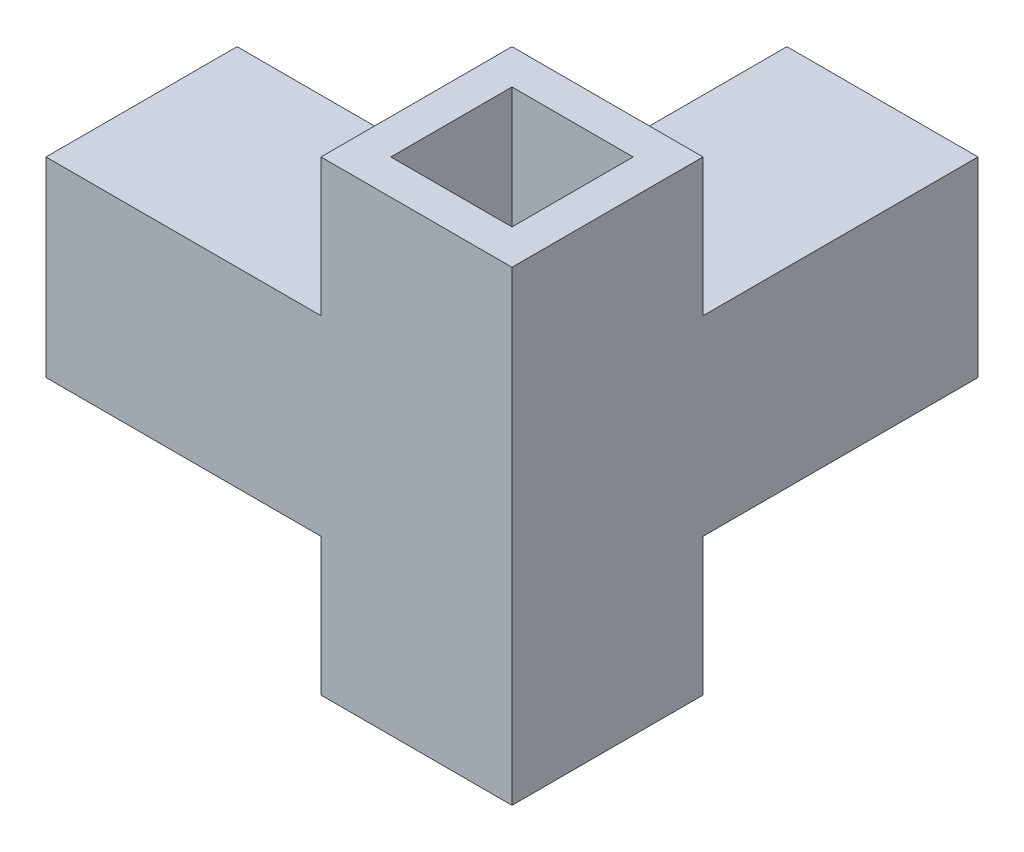
SolidWorks part; units mm, degrees
material "Ti-6Al-4VSolution treated and aged (SS)"
ref_plane "Front Plane" through (0, 0, 0) normal (0, 0, 1) x (1, 0, 0)
ref_plane "Top Plane" through (0, 0, 0) normal (0, 1, 0) x (1, 0, 0)
ref_plane "Right Plane" through (0, 0, 0) normal (1, 0, 0) x (0, 0, -1)
sketch "Sketch1" plane through (0, 0, 0) normal (1, 0, 0) x (0, 0, -1)
  line L0 (0, 0) -> (39.9501, 0) construction
  line L2 (0, 10) -> (0, -10)
  line L3 (0, -10) -> (8.2, -10)
  line L4 (8.2, 10) -> (8.2, 4.1)
  line L5 (0, 10) -> (8.2, 10)
  line L6 (8.2, -4.1) -> (20, -4.1)
  line L7 (8.2, 4.1) -> (20, 4.1)
  line L8 (0, 3.1861) -> (0, -3.1861)
  line L10 (20, 4.1) -> (20, -4.1)
  line L11 (8.2, -4.1) -> (8.2, -10)
  point P12 (0, -3.1861)
  point P14 (0, 0)
  dimension "D1" = 20
  dimension "D2" = 8.2
  dimension "D3" = 20
extrude "Boss-Extrude1" add sketch "Sketch1" along normal blind 8.2 contours L11 L3 L2 L5 L4 L7 L10 L6
shell "Shell1" thickness 1.5 removed face at (4.1, -10, -4.1) removed face at (4.1, 0, -20) removed face at (4.1, 10, -4.1)
sketch "Sketch2" plane through (0, 0, 0) normal (-1, 0, 0) x (0, 0, 1)
  line L0 (0, 10) -> (0, -10) construction
  line L1 (-8.2, 4.1) -> (0, 4.1)
  line L2 (-8.2, 4.1) -> (-8.2, -4.1)
  line L3 (-8.2, -4.1) -> (0, -4.1)
  line L4 (0, 4.1) -> (0, -4.1)
  point P7 (-8.2, -3.2904)
extrude "Boss-Extrude2" add sketch "Sketch2" along normal blind 11.8
shell "Shell2" thickness 1.5 removed face at (-11.8, 0, -4.1)
